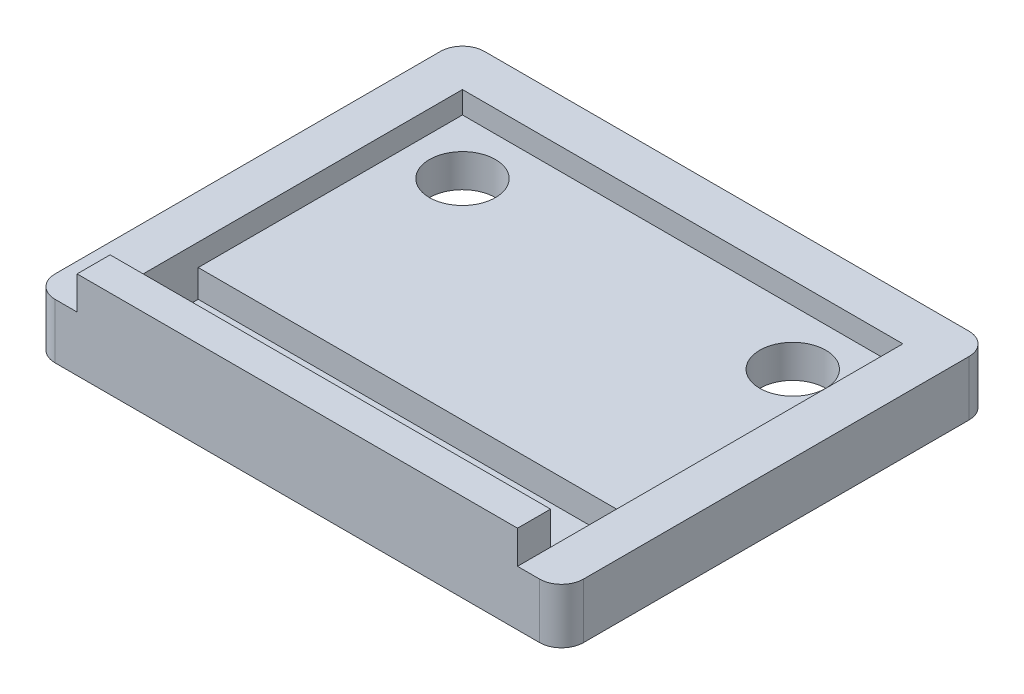
SolidWorks part; units mm, degrees
ref_plane "Front Plane" through (0, 0, 0) normal (0, 0, 1) x (1, 0, 0)
ref_plane "Top Plane" through (0, 0, 0) normal (0, 1, 0) x (1, 0, 0)
ref_plane "Right Plane" through (0, 0, 0) normal (1, 0, 0) x (0, 0, -1)
sketch "Sketch3" plane through (0, 0, 0) normal (0, 1, 0) x (1, 0, 0)
  line L0 (12, 17.5) -> (12, 1.5) construction
  line L1 (1, 0) -> (23, 0)
  line L2 (0, 1) -> (0, 18.5)
  line L3 (1, 19.5) -> (23, 19.5)
  line L4 (24, 1) -> (24, 18.5)
  line L5 (2, 1.5) -> (22, 1.5)
  line L6 (2, 1.5) -> (2, 17.5)
  line L7 (2, 17.5) -> (22, 17.5)
  line L8 (22, 1.5) -> (22, 17.5)
  line L9 (2, 1.5) -> (2, 0)
  line L10 (22, 1.5) -> (22, 0)
  line L11 (2, 5.5) -> (22, 5.5)
  circle A2 centre (4.5, 15) radius 1.5
  circle A3 centre (19.5, 15) radius 1.5
  arc A4 (23, 19.5) -> (24, 18.5) centre (23, 18.5) cw
  arc A5 (23, 0) -> (24, 1) centre (23, 1) ccw
  arc A6 (1, 0) -> (0, 1) centre (1, 1) cw
  arc A7 (0, 18.5) -> (1, 19.5) centre (1, 18.5) cw
  point P23 (24, 0)
  point P26 (0, 0)
  point P29 (0, 19.5)
  dimension "D3" = 2
  dimension "D4" = 1.5
  dimension "D5" = 2
  dimension "D7" = 3
  dimension "D8" = 2.5
  dimension "D9" = 2.5
  dimension "D12" = 1
  dimension "D1" = 24
  dimension "D2" = 19.5
  dimension "D6" = 2
  dimension "D10" = 2
  dimension "D11" = 2
  dimension "D13" = 4
extrude "Boss-Extrude2" add sketch "Sketch3" along normal blind 1.5 contours L0 L7 L6 L11 A2 | L7 L0 L11 L8 A3 region at (16.8435, 0, -11.2809) region at (7.1565, 0, -11.2809)
extrude "Boss-Extrude4" add sketch "Sketch3<5>" along normal blind 4 contours L10 L5 L9 L1 region at (12, 0, -0.75)
sketch "Sketch3<5>" plane through (0, 0, 0) normal (0, 1, 0) x (1, 0, 0) same geometry as "Sketch3"
extrude "Boss-Extrude5" add sketch "Sketch3<6>" along normal blind 0.25 contours L11 L0 L5 L8 | L0 L11 L6 L5 region at (17, 0, -3.5) region at (7, 0, -3.5)
sketch "Sketch3<6>" plane through (0, 0, 0) normal (0, 1, 0) x (1, 0, 0) same geometry as "Sketch3"
extrude "Boss-Extrude7" add sketch "Sketch3<8>" along normal blind 2.5 contours A7 L2 A6 L1 L9 L6 L7 L8 L10 A5 L4 A4 L3 region at (0.5116, 0, -0.5116)
sketch "Sketch3<8>" plane through (0, 0, 0) normal (0, 1, 0) x (1, 0, 0) same geometry as "Sketch3"
